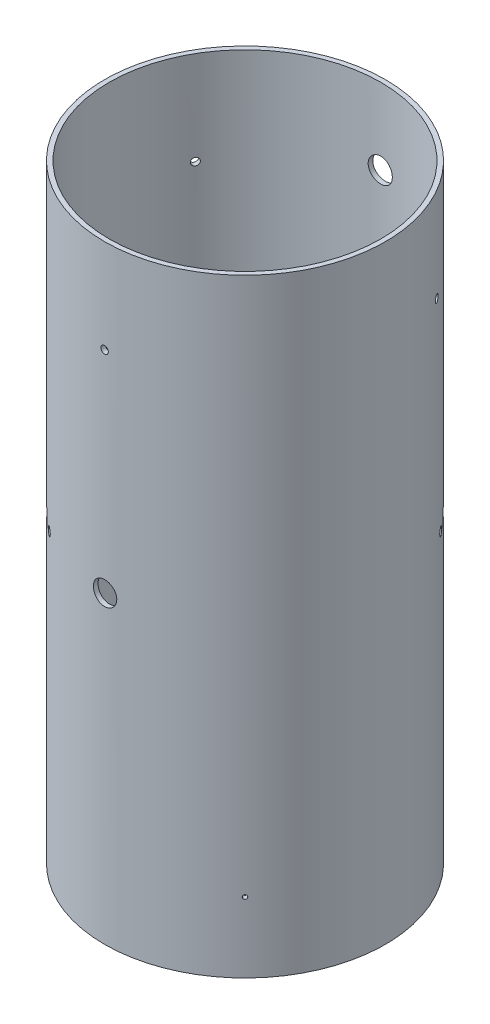
SolidWorks part; units mm, degrees
material "A-Glass Fiber"
ref_plane "Front Plane" through (0, 0, 0) normal (0, 0, 1) x (1, 0, 0)
ref_plane "Top Plane" through (0, 0, 0) normal (0, 1, 0) x (1, 0, 0)
ref_plane "Right Plane" through (0, 0, 0) normal (1, 0, 0) x (0, 0, -1)
sketch "Sketch1" plane through (0, 0, 0) normal (0, 1, 0) x (1, 0, 0)
  circle A0 centre (0, 0) radius 76.1746
  circle A1 centre (0, 0) radius 73.66
  dimension "D1" = 152.3492
  dimension "D2" = 147.32
extrude "Boss-Extrude1" add sketch "Sketch1" along normal blind 330.2
sketch "Sketch4" plane through (0, 0, 0) normal (0, 0, 1) x (1, 0, 0)
  line L0 (-76.1746, 0) -> (76.1746, 0) construction
  line L1 (76.1746, 330.2) -> (-76.1746, 330.2) construction
  line L2 (0, 330.2) -> (0, 0) construction
  line L3 (73.66, 330.2) -> (-73.66, 330.2) construction
  point P0 (0, 41.275)
  point P3 (0, 288.925)
  dimension "D1" = 41.275
  dimension "D2" = 41.275
hole_wizard "1/2 Clearance Hole5" positions "Sketch16" profile "Sketch17" hole size "1/2" standard "ANSI Inch"
sketch "Sketch16" plane through (0, 0, 0) normal (0, 0, 1) x (1, 0, 0)
  point P0 (0, 288.925)
sketch "Sketch17" plane through (0, 288.925, 0) normal (1, 0, 0) x (0, -1, 0)
  line L0 (0, 0) -> (0, 80.1345)
  line L1 (0, 80.1345) -> (6.5481, 76.2)
  line L2 (6.5481, 76.2) -> (6.5481, 0)
  line L5 (6.5481, 0) -> (0, 0)
  line L10 (0, 80.1345) -> (-6.5481, 76.2) construction
  line L11 (0, -6.35) -> (0, 107.95) construction
  dimension "Hole Dia." = 13.0962
  dimension "Hole Depth" = 76.2
  dimension "Drill Angle" = 118
sketch "Sketch27" plane through (0, 0, 0) normal (0, 0, 1) x (1, 0, 0)
  line L0 (0, 330.2) -> (0, 0) construction
  line L1 (-76.1746, 0) -> (76.1746, 0) construction
  circle A0 centre (0, 165.1) radius 6.35
  dimension "D1" = 12.7
  dimension "D2" = 165.1
extrude "Cut-Extrude1" cut sketch "Sketch27" against normal through all both and the other way through all
ref_plane "Plane1" through (0, 0, 0) normal (-0.7071, 0, 0.7071) x (0.7071, 0, 0.7071)
sketch "Sketch30" plane through (0, 0, 0) normal (-0.7071, 0, 0.7071) x (0.7071, 0, 0.7071)
  line L0 (0, 330.2) -> (0, 0) construction
  line L1 (4.953, 160.147) -> (-4.953, 160.147)
  line L2 (4.953, 160.147) -> (4.953, 170.053)
  line L3 (4.953, 170.053) -> (-4.953, 170.053)
  line L4 (-4.953, 160.147) -> (-4.953, 170.053)
  line L5 (4.953, 160.147) -> (-4.953, 170.053) construction
  line L6 (4.953, 170.053) -> (-4.953, 160.147) construction
  line L7 (-76.1746, 0) -> (76.1746, 0) construction
  circle A0 centre (-12.7, 165.1) radius 2.1831
  circle A1 centre (12.7, 165.1) radius 2.1831
  point P0 (0, 165.1)
  point P11 (0, 0)
  point P12 (0, 0)
  point P13 (0, 114.7812)
  dimension "D3" = 4.3663
  dimension "D4" = 4.3663
  dimension "D1" = 9.906
  dimension "D2" = 9.906
  dimension "D5" = 12.7
  dimension "D6" = 12.7
  dimension "D7" = 165.1
extrude "Cut-Extrude2" cut sketch "Sketch30" against normal through all both and the other way through all
sketch "Sketch23" plane through (0, 0, 0) normal (-0.7071, 0, 0.7071) x (0.7071, 0, 0.7071)
  line L0 (0, 0) -> (0, 330.2) construction
  line L1 (73.66, 330.2) -> (-73.66, 330.2) construction
  line L2 (-76.1746, 165.1) -> (76.1746, 165.1) construction
  line L3 (76.1746, 0) -> (76.1746, 330.2) construction
  circle A1 centre (0, 38.1) radius 1.0922
  point P12 (0, 165.1)
  dimension "D2" = 127
extrude "Shear Scrrews" cut sketch "Sketch23" against normal through all
pattern_circular "CirPattern1" count 4 over 360 about axis through (0, 330.2, 0) along (0, -1, 0) of "Shear Scrrews"
hole_wizard "Ø4.0 (4) Diameter Hole1" positions "Sketch24" profile "Sketch25" hole size "Ø4.0" standard "ANSI Metric"
sketch "Sketch24" plane through (0, 0, 0) normal (0, 0, 1) x (1, 0, 0)
  line L0 (76.1746, 330.2) -> (-76.1746, 330.2) construction
  point P0 (0, 279.4)
  dimension "D1" = 50.8
sketch "Sketch25" plane through (0, 279.4, 0) normal (1, 0, 0) x (0, 1, 0)
  line L0 (0, 0) -> (0, 90.1017)
  line L1 (0, 90.1017) -> (2, 88.9)
  line L2 (2, 88.9) -> (2, 0)
  line L5 (2, 0) -> (0, 0)
  line L10 (0, 90.1017) -> (-2, 88.9) construction
  line L11 (0, -6.35) -> (0, 107.95) construction
  dimension "Hole Dia." = 4
  dimension "Hole Depth" = 88.9
  dimension "Drill Angle" = 118
pattern_circular "CirPattern2" count 3 over 360 about axis through (0, 330.2, 0) along (0, 1, 0) of "Ø4.0 (4) Diameter Hole1"
equation "\"Mid_Coupler_Length\" = 13in"
equation "\"D1@Boss-Extrude1\"=\"Mid_Coupler_Length\""
equation "\"Shear_Screw_Coupler_Location\" = 4.5in"
equation "\"Shear_Screw_Diameter\" = 0.086in"
equation "\"D2@Sketch23\"=\"Shear_Screw_Coupler_Location\"+0.5"
equation "\"Mid_Tube_Length\"= 1in"
equation "\"Bodytube_OD\" = 6.17in"
equation "\"Bodytube_ID\" = 5.998in"
equation "\"Camera_Cutout_Width\"=10mm"
equation "\"Camera_Cutout_Height\"=7mm"
equation "\"Fwd_Tube_Length\" = 40in"
equation "\"BKHD_Screw_Diam\"= 3.5mm"
equation "\"Fwd_BKHD_From_Top\" = 18in"
equation "\"Motor_OD\" = 4in"
equation "\"Aft_Section_Length\"= 39in"
equation "\"AB_Coupler_OD_Length\"= 1in"
equation "\"AB_Coupling_Section_Length\"= 0.375in"
equation "\"AB_Coupler_Length\"= \"AB_Coupler_OD_Length\" + \"AB_Coupling_Section_Length\" * 2"
equation "\"Cutout_Angle\" = 80"
equation "\"AB_Paddle_Height\" = 0.375in"
equation "\"AB_Coupler_Num_Screws\"= 4"
equation "\"AB_BKHD_Thickness\" = 0.375in"
equation "\"AB_Mount_From_Bottom\" = 23.175in"
equation "\"Num_Cutouts\" = 3"
equation "\"AB_Coupler_OD\"= 6.17in"
equation "\"AB_Coupler_ID\"= 5.75in"
equation "\"AB_Coupler_Surface_Diameter\"= 5.998in"
equation "\"AB_Coupling_Screw_Diameter\"= 0.15748in"
equation "\"AB_Central_Bushing_Length\" = .4724in"
equation "\"Lead_Screw_Dist\" = 3.4in"
equation "\"Lead_Screw_Diam\" = 0.386in"
equation "\"Lead_Screw_Length\" = (\"Mid_Coupler_Length\" + 2*0.375in + 2*0.5in)"
equation "\"Paddle_Pin_Offset\" = .25in"
equation "\"Paddle_Pin_Radius\" = 2.25in"
equation "\"SS_Paddle_Pin_Radius\" = 2.25*0.66in"
equation "\"Paddle_Gear_OD\" = 3.2in"
equation "\"Drive_Gear_OD\" = 1.7in"
equation "\"Fin_Thickness\"= .118in"
equation "\"Guiderail_Cutout_Diameter\"= 1.5in"
equation "\"DB9_Hole_Dist\" = 25mm"
equation "\"DB9_Relief_Width\" = 0.47in"
equation "\"DB9_Relief_Hole_Offset\" = 0.09in"
equation "\"Airbrakes_Wire_Hole_Dia\" = .25in"
equation "\"Airbrakes_Wire_Hole_Dist\" = 1.1in"
equation "\"Servo_Gear_Offset\" = 0.5in"
equation "\"FWD_Shear_Screw_Dist\" = 1.5in"
equation "\"Camera_Screw_Dia\" = 0.216535"
equation "\"Camera_Hole_Angle\" = atn ( 2 / 3 * tan ( 12.5deg ) )"
equation "\"D1@Sketch26\"=\"Camera_Cutout_Height\""
equation "\"D2@Sketch26\"=\"Camera_Cutout_Width\""
equation "\"D3@Sketch26\"=6.125"
equation "\"D1@Sketch28\"=\"Camera_Screw_Dia\""
equation "\"D2@CirPattern3\"=\"Camera_Hole_Angle\""
equation "\"D1@Sketch29\"=\"Camera_Screw_Dia\""
equation "\"D2@CirPattern4\"=\"Camera_Hole_Angle\""
equation "\"Coupler_OD\" = 5.998"
equation "\"D1@Sketch1\"=\"Coupler_OD\""
equation "\"Coupler_ID\" = 5.8"
equation "\"D2@Sketch1\"=\"Coupler_ID\""
